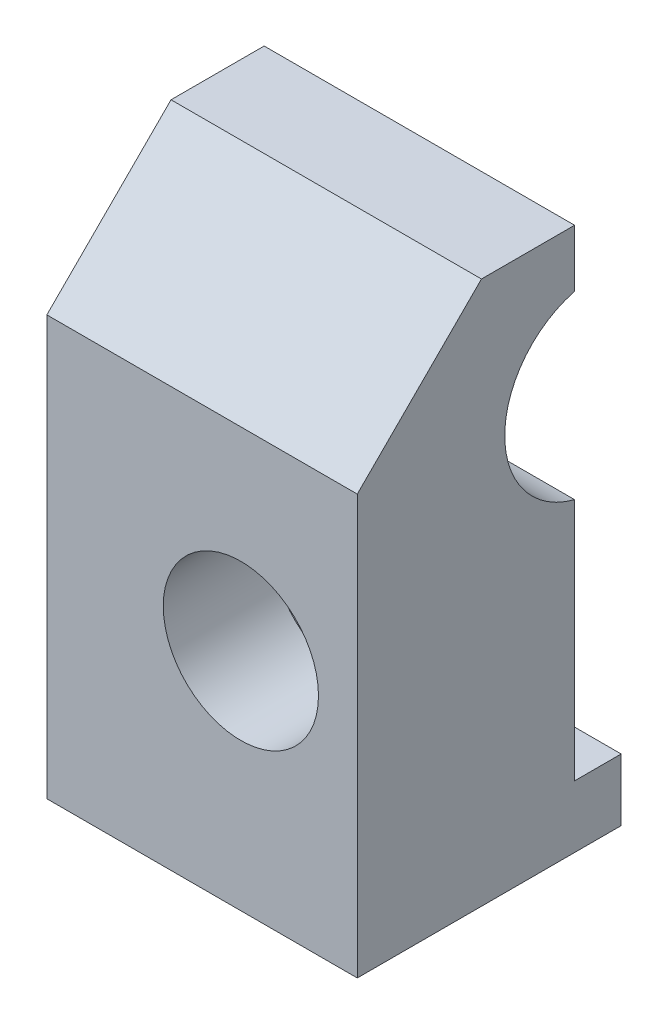
SolidWorks part; units mm, degrees
material "3D printed plastic"
ref_plane "Front Plane" through (0, 0, 0) normal (0, 0, 1) x (1, 0, 0)
ref_plane "Top Plane" through (0, 0, 0) normal (0, 1, 0) x (1, 0, 0)
ref_plane "Right Plane" through (0, 0, 0) normal (1, 0, 0) x (0, 0, -1)
sketch "Sketch1" plane through (0, 0, 0) normal (0, 0, 1) x (1, 0, 0)
  line L0 (0, 0) -> (0, -44.5) construction
  line L1 (-15, 14.5) -> (15, 14.5)
  line L2 (-15, 14.5) -> (-15, -44.5)
  line L3 (-15, -44.5) -> (15, -44.5)
  line L4 (15, 14.5) -> (15, -44.5)
  circle A0 centre (0, 0) radius 7
  dimension "D1" = 30
  dimension "D4" = 14
  dimension "D2" = 14.5
  dimension "D3" = 59
extrude "Boss-Extrude1" add sketch "Sketch1" against normal blind 30
sketch "Sketch2" plane through (0, -44.5, 0) normal (0, -1, 0) x (1, 0, 0)
  line L0 (-15, -30) -> (-15, 0) construction
  line L2 (-15, -30) -> (15, -30) construction
  line L5 (15, -30) -> (15, 0) construction
  line L6 (-15, -30) -> (15, -30)
  line L7 (-15, -30) -> (-15, -28)
  line L8 (-15, -28) -> (15, -28)
  line L9 (15, -30) -> (15, -28)
  dimension "D1" = 2
extrude "Cut-Extrude1" cut sketch "Sketch2" against normal mid plane 8 from offset 14.5 offset against normal yes
sketch "Sketch4" plane through (0, 0, 0) normal (0, 0, 1) x (1, 0, 0)
  line L0 (-15, -44.5) -> (15, -44.5) construction
  line L1 (-15, 14.5) -> (30, 14.5)
  line L2 (-15, 14.5) -> (-15, -44.5)
  line L3 (-15, -44.5) -> (30, -44.5)
  line L4 (30, 14.5) -> (30, -44.5)
  line L5 (15, -44.5) -> (15, 14.5) construction
  circle A0 centre (0, 0) radius 7
  circle A2 centre (0, 0) radius 7 construction
  dimension "D1" = 15
extrude "Boss-Extrude2" add sketch "Sketch4" along normal blind 12
sketch "Sketch5" plane through (0, 0, 12) normal (0, 0, 1) x (1, 0, 0)
  circle A0 centre (0, 0) radius 8
  dimension "D1" = 16
extrude "Cut-Extrude3" cut sketch "Sketch5" against normal blind 8.5
sketch "Sketch8" plane through (0, 0, 12) normal (0, 0, 1) x (1, 0, 0)
  circle A0 centre (0, 0) radius 10
  dimension "D1" = 20
extrude "Cut-Extrude5" cut sketch "Sketch8" against normal blind 3.5
sketch "Sketch11" plane through (0, 0, 12) normal (0, 0, 1) x (1, 0, 0)
  line L0 (-15, -44.5) -> (30, -44.5) construction
  line L1 (30, 14.5) -> (8, 14.5)
  line L2 (30, 14.5) -> (30, -44.5)
  line L3 (30, -44.5) -> (8, -44.5)
  line L4 (8, 14.5) -> (8, 6)
  line L9 (8, -6) -> (8, -44.5)
  arc A0 (8, -6) -> (8, 6) centre (0, 0) ccw
  circle A1 centre (0, 0) radius 10 construction
  dimension "D1" = 22
extrude "Boss-Extrude4" add sketch "Sketch11" along normal blind 1.5
sketch "Sketch12" plane through (30, 0, 0) normal (1, 0, 0) x (0, 0, -1)
  line L0 (-13.5, -44.5) -> (-13.5, 14.5) construction
  line L1 (0, -19) -> (-15, -19) construction
  line L3 (0, -44.5) -> (0, 14.5) construction
  line L4 (30, -44.5) -> (0, -44.5) construction
  circle A0 centre (-15, -19) radius 6
  dimension "D1" = 12
  dimension "D2" = 1.5
  dimension "D3" = 25.5
extrude "Cut-Extrude7" cut sketch "Sketch12" against normal up to surface (22 mm away) up to face at (8, -20.4375, 13.125)
chamfer "Chamfer1" distance 2 angle 45 3 edges
other "Move Face1" face at (8, -19, 10.5) offset 1 parameters "D1"=1
sketch "Sketch16" plane through (30, 0, 0) normal (1, 0, 0) x (0, 0, -1)
  line L0 (0, -44.5) -> (0, 14.5) construction
  line L1 (0, 4) -> (1, 4)
  line L2 (0, 4) -> (0, -4)
  line L3 (0, -4) -> (1, -4)
  line L4 (1, 4) -> (1, -4)
  line L5 (1, 0) -> (1, -30) construction
  line L6 (0, -26) -> (1, -26)
  line L7 (0, -26) -> (0, -34)
  line L8 (0, -34) -> (1, -34)
  line L9 (1, -26) -> (1, -34)
  line L10 (1, -15) -> (0, -15) construction
  dimension "D1" = 8
  dimension "D2" = 1
  dimension "D3" = 30
extrude "Boss-Extrude5" add sketch "Sketch16" against normal up to surface (15 mm away) up to face at (15, -26.1875, -25.75)
sketch "Sketch14" plane through (0, 0, 13.5) normal (0, 0, 1) x (1, 0, 0)
  line L0 (22.5, -30) -> (22.5, 0) construction
  line L1 (22.5, -15) -> (-15, -15) construction
  line L2 (-15, 14.5) -> (-15, -44.5) construction
  line L4 (30, -13.1905) -> (30, 14.5) construction
  circle A0 centre (22.5, 0) radius 2.25
  circle A1 centre (22.5, -30) radius 2.25
  dimension "D1" = 30
  dimension "D3" = 4.5
  dimension "D2" = 7.5
extrude "Cut-Extrude9" cut sketch "Sketch14" against normal through all
sketch "Sketch17" plane through (30, 0, 0) normal (1, 0, 0) x (0, 0, -1)
  line L0 (-16.5, -13.1905) -> (-16.5, -9.5)
  line L2 (-30.5, -9.5) -> (-30.5, -44.5)
  line L3 (-30.5, -44.5) -> (-13.5, -44.5)
  line L4 (-16.5, -40.5) -> (-16.5, -24.8095)
  line L5 (-15, -19) -> (-15, -10.6102) construction
  line L6 (-13.5, -13.1905) -> (-13.5, 14.5) construction
  line L8 (-13.5, -44.5) -> (0, -44.5) construction
  line L9 (-13.5, -44.5) -> (-13.5, -40.5)
  line L10 (-13.5, -44.5) -> (-13.5, -24.8095) construction
  line L12 (-16.5, -9.5) -> (-30.5, -9.5)
  line L13 (-13.5, -40.5) -> (-16.5, -40.5)
  arc A0 (-16.5, -13.1905) -> (-16.5, -24.8095) centre (-15, -19) ccw
  dimension "D1" = 14
  dimension "D2" = 4
  dimension "D3" = 35
extrude "Boss-Extrude6" add sketch "Sketch17" against normal blind 20 separate body
sketch "Sketch18" plane through (0, 0, 13.5) normal (0, 0, 1) x (1, 0, 0)
  circle A0 centre (22.5, 0) radius 5
  dimension "D1" = 10
extrude "Cut-Extrude10" cut sketch "Sketch18" against normal blind 3
sketch "Sketch19" plane through (0, 0, 30.5) normal (0, 0, 1) x (1, 0, 0)
  circle A0 centre (22.5, -30) radius 2.25
  circle A1 centre (22.5, -30) radius 2.25 construction
extrude "Cut-Extrude11" cut sketch "Sketch19" against normal through all
sketch "Sketch20" plane through (0, 0, 30.5) normal (0, 0, 1) x (1, 0, 0)
  circle A0 centre (22.5, -30) radius 5
  circle A2 centre (22.5, 0) radius 5 construction
extrude "Cut-Extrude12" cut sketch "Sketch20" against normal blind 7
chamfer "Chamfer2" distance 8 angle 45 1 edges at (20, -9.5, 30.5)
sketch "Sketch21" plane through (15, 0, 0) normal (1, 0, 0) x (0, 0, -1)
  line L0 (0, 4) -> (0, 14.5) construction
  line L1 (0, 9) -> (10, 9)
  line L2 (0, 9) -> (0, 4)
  line L3 (0, -9) -> (10, -9)
  line L4 (10, 9) -> (10, -9)
  line L5 (0, -26) -> (0, -4) construction
  line L6 (0, -21) -> (10, -21)
  line L7 (0, -21) -> (0, -26)
  line L8 (0, -39) -> (10, -39)
  line L9 (10, -21) -> (10, -39)
  line L10 (0, -4) -> (0, -9)
  line L11 (1, -26) -> (0, -26)
  line L12 (1, -26) -> (1, -34)
  line L13 (1, -34) -> (0, -34)
  line L15 (1, 4) -> (0, 4)
  line L16 (1, 4) -> (1, -4)
  line L17 (1, -4) -> (0, -4)
  line L18 (0, -34) -> (0, -39)
  dimension "D1" = 18
  dimension "D2" = 10
extrude "Cut-Extrude13" cut sketch "Sketch21" against normal blind 2
sketch "Sketch22" plane through (0, 0, -28) normal (0, 0, -1) x (-1, 0, 0)
  line L0 (-0.0016, -30) -> (15, -30) construction
  line L1 (15, -26) -> (15, -34) construction
  circle A0 centre (-0.0016, -30) radius 3.3
  dimension "D1" = 6.6
  dimension "D2" = 15.0016
extrude "Cut-Extrude14" cut sketch "Sketch22" against normal blind 15
sketch "Sketch23" plane through (0, 0, -28) normal (0, 0, -1) x (-1, 0, 0)
  line L0 (-5.1016, -32.9445) -> (-5.1016, -44.5)
  line L1 (-0.0016, -35.889) -> (5.0984, -32.9445) construction
  line L2 (5.0984, -32.9445) -> (5.0984, -27.0555)
  line L3 (5.0984, -27.0555) -> (-0.0016, -24.111)
  line L4 (-0.0016, -24.111) -> (-5.1016, -27.0555)
  line L5 (-5.1016, -27.0555) -> (-5.1016, -32.9445)
  line L6 (-5.1016, -32.9445) -> (-0.0016, -35.889) construction
  line L7 (15, -44.5) -> (-15, -44.5) construction
  line L8 (-5.1016, -44.5) -> (5.0984, -44.5)
  line L9 (5.0984, -44.5) -> (5.0984, -32.9445)
  circle A0 centre (-0.0016, -30) radius 5.1 construction
  dimension "D1" = 10.2
extrude "Cut-Extrude15" cut sketch "Sketch23" against normal blind 7 from offset 3 offset against normal yes
sketch "Sketch24" plane through (15, 0, 0) normal (1, 0, 0) x (0, 0, -1)
  line L0 (30, 14.5) -> (0, 14.5) construction
  line L1 (11, 14.5) -> (19, 14.5)
  line L2 (11, 14.5) -> (11, 10.5)
  line L3 (11, 10.5) -> (19, 10.5)
  line L4 (19, 14.5) -> (19, 10.5)
  line L5 (30, -26) -> (30, 14.5) construction
  line L6 (30, 4) -> (26, 4)
  line L7 (30, 4) -> (30, -4)
  line L8 (30, -4) -> (26, -4)
  line L9 (26, 4) -> (26, -4)
  line L10 (30, 0) -> (26, 0) construction
  line L11 (15, 14.5) -> (15, 10.5) construction
  line L12 (0, 9) -> (0, 14.5) construction
  dimension "D1" = 8
  dimension "D2" = 4
  dimension "D3" = 15
  dimension "D4" = 14.5
extrude "Boss-Extrude7" add sketch "Sketch24" along normal blind 4
sketch "Sketch25" plane through (0, 0, -30) normal (0, 0, -1) x (-1, 0, 0)
  line L0 (-8.1915, 5.7358) -> (-12.2077, 0)
  line L1 (-12.2077, 0) -> (-8.1915, -5.7358)
  line L2 (-12.2077, 0) -> (0, 0) construction
  arc A0 (-8.1915, -5.7358) -> (-8.1915, 5.7358) centre (0, 0) ccw
  dimension "D1" = 20
  dimension "D2" = 110
extrude "Cut-Extrude16" cut sketch "Sketch25" against normal offset from surface (31.5 mm away) 2 up to face at (8, 0, 3.5)
delete or keep bodies "Body-Delete1" type delete bodies bodies 126
